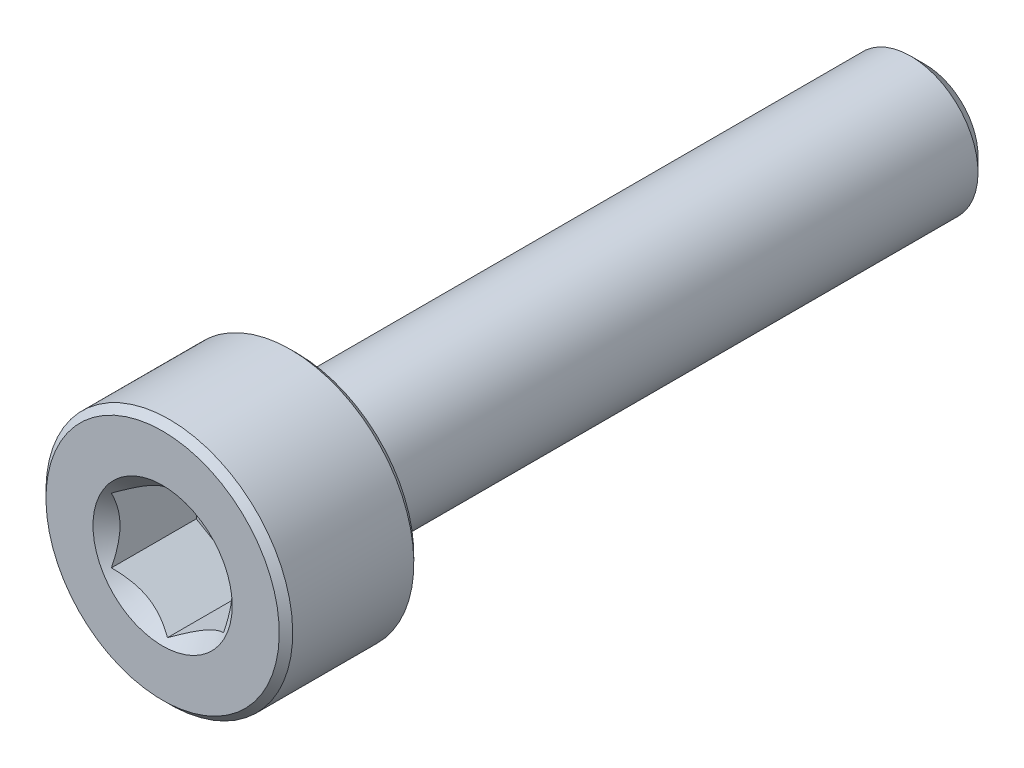
SolidWorks part; units mm, degrees
ref_plane "Front Plane" through (0, 0, 0) normal (0, 0, 1) x (1, 0, 0)
ref_plane "Top Plane" through (0, 0, 0) normal (0, 1, 0) x (1, 0, 0)
ref_plane "Right Plane" through (0, 0, 0) normal (1, 0, 0) x (0, 0, -1)
sketch "Sketch1" plane through (0, 0, 0) normal (1, 0, 0) x (0, 0, -1)
  line L0 (-8.5, 0) -> (8.5, 0) construction
  line L1 (8.5, 0) -> (8.5, 1.1752) construction
  line L2 (8.5, 1.1752) -> (8.1752, 1.5) construction
  line L3 (8.1752, 1.5) -> (8.125, 1.5) construction
  line L4 (8.125, 1.5) -> (-5.5, 1.5) construction
  line L5 (-5.5, 1.5) -> (-5.5, 2.75) construction
  line L6 (-5.5, 2.75) -> (-8.5, 2.75) construction
  line L7 (-8.5, 2.75) -> (-8.5, 0) construction
  line L8 (8.5, 1.1752) -> (8.5, 1.5) construction
  line L9 (8.4688, 1.5541) -> (8.7188, 1.1211) construction
  line L10 (8.7188, 1.1211) -> (8.9688, 1.5541) construction
  line L11 (8.9688, 1.5541) -> (8.4688, 1.5541) construction
  line L12 (8.7188, 1.5541) -> (8.7188, 1.5) construction
  line L13 (8.7188, 1.1211) -> (8.7188, 1.1752) construction
  line L14 (8.6875, 1.1752) -> (8.75, 1.1752) construction
  line L15 (8.5, 1.5) -> (8.9375, 1.5) construction
  line L16 (8.4844, 1.5271) -> (8.9531, 1.5271) construction
  line L17 (8.5, 0) -> (8.5, -1.5) construction
  line L18 (-5.65, 2.75) -> (-5.5, 2.6) construction
  line L19 (-8.35, 2.75) -> (-8.5, 2.6) construction
  line L20 (-5.5, 1.5) -> (-5.5, 0) construction
  line L21 (-5.5, 0.75) -> (-0.8333, 0.75) construction
  line L22 (-0.8333, 0.75) -> (3.8333, 0.75) construction
  line L23 (3.8333, 0.75) -> (8.5, 0.75) construction
  line L24 (-0.8333, 0.75) -> (-0.8333, 1.5) construction
  line L25 (-0.8333, 1.5) -> (-0.8333, 2.75) construction
  line L26 (3.8333, 0.75) -> (3.8333, 2.75) construction
  point P0 (-8.5, 1.25)
  point P3 (7.25, 1.5)
  point P4 (0, 0)
  point P18 (3.8333, 1.5)
  point P22 (8.7188, 1.1752)
  point P24 (8.125, 1.5)
  point P25 (8.7188, 1.5)
  point P28 (8.7188, 1.5271)
  point P29 (7.25, -1.5)
  point P30 (-0.8333, 1.5)
  point P31 (-7, 2.75)
  point P37 (-6.025, 2.75)
  point P38 (-8.275, 2.75)
  point P45 (-0.8333, 0.75)
  point P46 (3.8333, 0.75)
  dimension "D2" = 0.0625
  dimension "D7" = 0.15
  dimension "D8" = 0.15
  dimension "D9" = 0.15
  dimension "D10" = 0.075
  dimension "D11" = 0.375
  dimension "Drive Size" = 2.5
  dimension "Head Diameter" = 5.5
  dimension "Head Height" = 3
  dimension "Thread Pitch" = 0.5
  dimension "Thread Dia" = 3
  dimension "Length" = 14
  dimension "D12" = 0.375
  dimension "D4" = 1.25
  dimension "D3" = 45
sketch "Sketch2" plane through (0, 0, 0) normal (1, 0, 0) x (0, 0, -1)
  line L0 (-8.5, 0) -> (-8.5, 2.6)
  line L1 (-8.35, 2.75) -> (-5.65, 2.75)
  line L2 (-5.5, 2.6) -> (-5.5, 1.65)
  line L4 (8.1752, 1.5) -> (8.5, 1.1752)
  line L5 (8.5, 1.1752) -> (8.5, 0)
  line L6 (-5.5, 2.75) -> (-8.5, 2.75) construction
  line L7 (8.5, 0) -> (-8.5, 0)
  line L8 (-8.35, 2.75) -> (-8.5, 2.6) construction
  line L10 (-8.35, 2.75) -> (-8.5, 2.6)
  line L14 (-5.65, 2.75) -> (-5.5, 2.6) construction
  line L16 (-5.65, 2.75) -> (-5.5, 2.6)
  line L17 (-5.5, 1.5) -> (-5.5, 2.75) construction
  line L19 (-5.35, 1.5) -> (8.1752, 1.5)
  line L20 (8.125, 1.5) -> (-5.5, 1.5) construction
  arc A1 (-5.5, 1.65) -> (-5.35, 1.5) centre (-5.35, 1.65) ccw
  dimension "D3" = 0.15
revolve "Revolve1" add sketch "Sketch2" angle 360 about L7
sketch "Sketch3" plane through (0, 0, 8.5) normal (0, 0, 1) x (1, 0, 0)
  line L1 (1.25, -0.7217) -> (1.25, 0.7217)
  line L2 (1.25, 0.7217) -> (0, 1.4434)
  line L3 (0, 1.4434) -> (-1.25, 0.7217)
  line L4 (-1.25, 0.7217) -> (-1.25, -0.7217)
  line L5 (-1.25, -0.7217) -> (0, -1.4434)
  line L6 (0, -1.4434) -> (1.25, -0.7217)
  circle A0 centre (0, 0) radius 1.25 construction
  circle A1 centre (0, 0) radius 2.75 construction
  circle A2 centre (0, 0) radius 2.75 construction
  circle A3 centre (0, 0) radius 1.4434 construction
  point P13 (0, 0)
  dimension "D1" = 2.8868
extrude "Cut-Extrude1" cut sketch "Sketch3" against normal offset from surface (2 mm away) 1 up to face at (0, 2.6, 5.5)
sketch "Sketch4" plane through (0, 0, 8.5) normal (0, 0, 1) x (1, 0, 0)
  circle A0 centre (0, 0) radius 1.5516
  dimension "D1" = 3.1033
extrude "Cut-Extrude2" cut sketch "Sketch4" against normal up to vertex (1.5 mm away) draft 45 up to point (0, 2.75, 7)
sketch "Sketch11" plane through (0, 0, 0) normal (1, 0, 0) x (0, 0, -1)
  line L0 (-8.5, 0) -> (8.5, 0) construction
  line L1 (-8.5, 0) -> (8.5, 0) construction
  line L2 (-2.875, 0) -> (-2.875, 1.5) construction
  line L3 (8.125, 1.5) -> (-5.5, 1.5) construction
  line L4 (5.875, 0) -> (5.875, 1.5) construction
  line L6 (8.5, 1.1752) -> (8.5, 1.5) construction
  point P2 (-2.875, 0)
  point P3 (5.875, 0)
  dimension "D1" = 2.625
  dimension "D2" = 2.625
sketch "Sketch6" [suppressed] plane through (0, 0, -8.5) normal (0, 0, -1) x (-1, 0, 0)
  circle A0 centre (0, 0) radius 1.5
curve "Helix/Spiral1" [suppressed] pitch 0.5 height 14.5 turns 29
sketch "Sketch10" [suppressed] plane through (0, 0, 0) normal (1, 0, 0) x (0, 0, -1)
  line L0 (-5.35, -2.75) -> (-5.35, 2.75)
  line L5 (-8.5, 0) -> (8.5, 0) construction
  line L6 (-5.35, 1.5) -> (-5.35, -1.5) construction
  point P3 (-5.35, 0)
split "Split1" [suppressed] bodies to split 106
sketch "Sketch7" [suppressed] plane through (0, 0, 0) normal (1, 0, 0) x (0, 0, -1)
  line L0 (8.4844, 1.5271) -> (8.9531, 1.5271)
  line L1 (8.9531, 1.5271) -> (8.75, 1.1752)
  line L2 (8.75, 1.1752) -> (8.6875, 1.1752)
  line L3 (8.6875, 1.1752) -> (8.4844, 1.5271)
sweep "Cut-Sweep1" [suppressed] cut profiles "Sketch7" path "Helix/Spiral1"
sketch "Sketch8" [suppressed] plane through (0, 0, 0) normal (1, 0, 0) x (0, 0, -1)
  line L0 (-5.5, 0) -> (-5.5, 1.5)
  line L1 (-5.35, -1.5) -> (-5.35, 1.5) construction
  line L2 (-5.5, 1.5) -> (-5.35, 1.5)
  line L4 (-5.35, 1.5) -> (-4.484, 0)
  line L5 (-4.484, 0) -> (-5.5, 0)
  line L6 (8.125, 1.5) -> (-5.5, 1.5) construction
  line L7 (-8.5, 0) -> (8.5, 0) construction
  dimension "D1" = 60
revolve "Revolve2" [suppressed] add sketch "Sketch8" angle 360 about L5
equation "\"D2@Sketch1\" = \"Thread Pitch@Sketch1\" / 8"
equation "\"D4@Helix/Spiral1\" = \"Thread Pitch@Sketch1\""
equation "\"D7@Sketch1\" = \"Head Height@Sketch1\" * .05"
equation "\"D8@Sketch1\"=\"D7@Sketch1\""
equation "\"D9@Sketch1\"=\"D7@Sketch1\""
equation "\"D10@Sketch1\"=\"D7@Sketch1\"/2"
equation "\"D11@Sketch1\"=\"D10@Sketch1\"*5"
equation "\"D4@Sketch1\"=\"Thread Pitch@Sketch1\"*2.5"
equation "\"D12@Sketch1\"=\"Thread Pitch@Sketch1\"*.75"
equation "\"D3@Helix/Spiral1\"=\"Length@Sketch1\"+\"Thread Pitch@Sketch1\""
equation "\"D3@Sketch2\"=\"Thread Dia@Sketch1\"*0.05"
equation "\"D1@Sketch11\"=\"Length@Sketch1\"*0.1875"
equation "\"D2@Sketch11\"=\"D1@Sketch11\""
equation "\"D1@Sketch4\"=\"D1@Sketch3\"*1.075"
